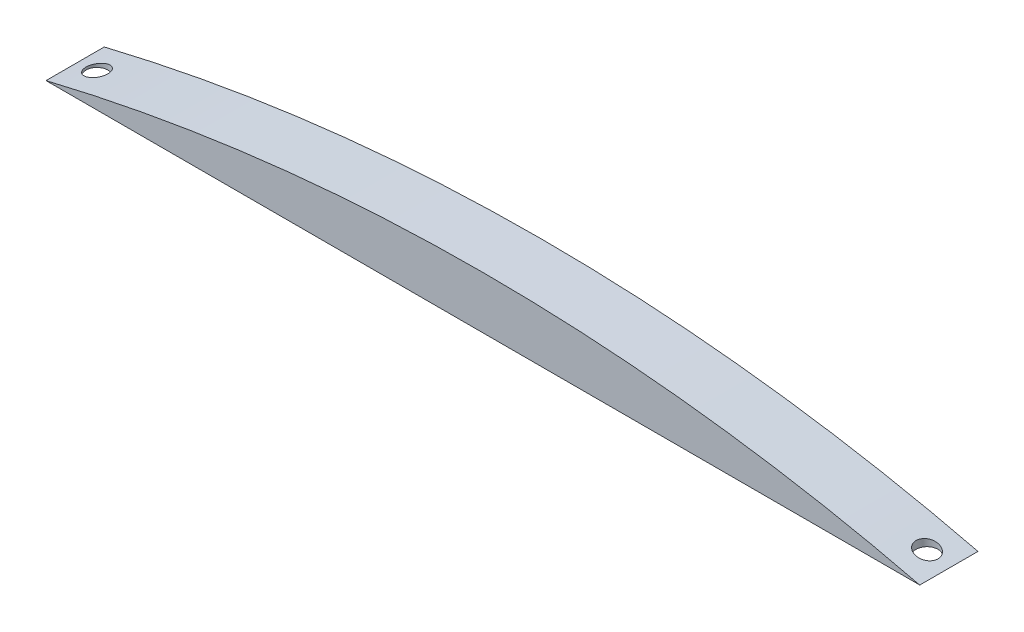
SolidWorks part; units mm, degrees
ref_plane "Front Plane" through (0, 0, 0) normal (0, 0, 1) x (1, 0, 0)
ref_plane "Top Plane" through (0, 0, 0) normal (0, 1, 0) x (1, 0, 0)
ref_plane "Right Plane" through (0, 0, 0) normal (1, 0, 0) x (0, 0, -1)
sketch "Sketch1" plane through (0, 0, 0) normal (0, 0, 1) x (1, 0, 0)
  line L0 (-190.5, 0) -> (190.5, 0)
  line L1 (-180.975, 0) -> (180.975, 0)
  arc A0 (-190.5, 0) -> (190.5, 0) centre (0, -783.7652) cw
  point P4 (0, 0)
  point P8 (0, 0)
extrude "Boss-Extrude3" add sketch "Sketch1" along normal blind 25.4 contours A0 L0 region at (0, 9.1388, 0)
sketch "Sketch2" plane through (0, 0, 0) normal (0, -1, 0) x (1, 0, 0)
  line L0 (0, 25.4) -> (0, 0) construction
  line L1 (-190.5, 25.4) -> (190.5, 25.4) construction
  line L2 (-180.975, 12.7) -> (180.975, 12.7)
  circle A0 centre (-180.975, 12.7) radius 4.7625
  circle A1 centre (180.975, 12.7) radius 4.7625
  point P8 (0, 12.7)
  dimension "D1" = 9.525
  dimension "D2" = 9.525
extrude "Cut-Extrude1" cut sketch "Sketch2" against normal blind 25.4 contours A0 | A1 region at (180.975, 0, 17.3278) region at (-185.6028, 0, 12.7)
